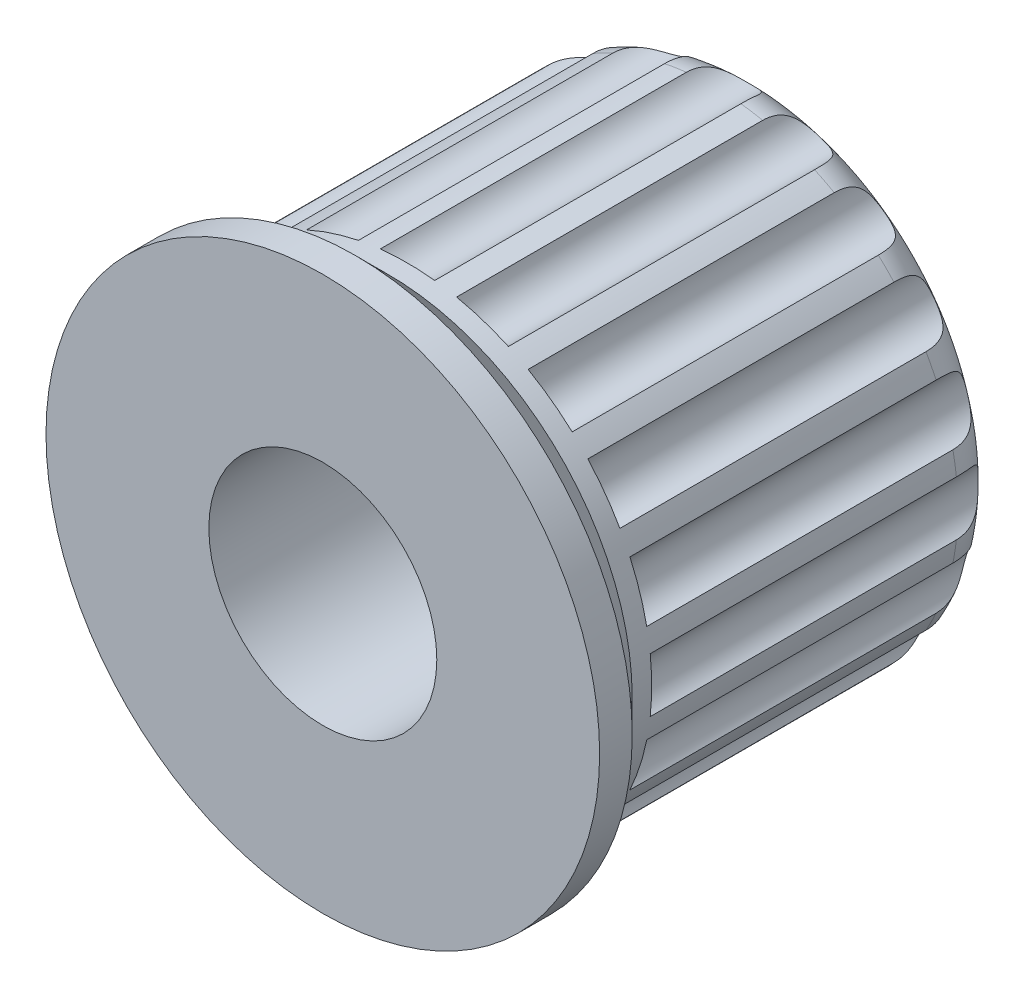
SolidWorks part; units mm, degrees
ref_plane "Front Plane" through (0, 0, 0) normal (0, 0, 1) x (1, 0, 0)
ref_plane "Top Plane" through (0, 0, 0) normal (0, 1, 0) x (1, 0, 0)
ref_plane "Right Plane" through (0, 0, 0) normal (1, 0, 0) x (0, 0, -1)
sketch "Sketch1" plane through (0, 0, 0) normal (0, 0, 1) x (1, 0, 0)
  circle A0 centre (0, 0) radius 2.975
  circle A1 centre (0, 0) radius 7.5
  dimension "D1" = 5.95
  dimension "D2" = 15
extrude "Boss-Extrude1" add sketch "Sketch1" along normal blind 2 contours A0 region at (0, 0, 0)
extrude "Boss-Extrude3" add sketch "Sketch1<3>" along normal offset from surface (13.5 mm away) 11.5 up to face at (2.975, 0, 2) offset beyond the face yes
sketch "Sketch1<3>" plane through (0, 0, 0) normal (0, 0, 1) x (1, 0, 0) same geometry as "Sketch1"
sketch "Sketch2" plane through (0, 0, 13.5) normal (0, 0, 1) x (1, 0, 0)
  circle A0 centre (0, 0) radius 3.5
  circle A1 centre (0, 0) radius 2.975 construction
  circle A2 centre (0, 0) radius 2.975
  dimension "D1" = 7
extrude "Cut-Extrude1" cut sketch "Sketch2" against normal offset from surface (5.5 mm away) 6 up to face at (2.975, 0, 2)
sketch "Sketch3" plane through (0, 0, 13.5) normal (0, 0, 1) x (1, 0, 0)
  circle A0 centre (0, 0) radius 7.5 construction
  circle A1 centre (0, 0) radius 7.5
  circle A2 centre (0, 0) radius 8.5
  dimension "D1" = 17
extrude "Boss-Extrude4" add sketch "Sketch3" against normal blind 2
fillet "Fillet2" radius 1.5 1 edges at (7.5, 0, 0)
sketch "Sketch5" plane through (0, 0, 0) normal (0, 0, -1) x (-1, 0, 0)
  circle A0 centre (0, 8) radius 1
  circle A2 centre (0, 0) radius 7.5 construction
  dimension "D2" = 2
  dimension "D1" = 0.5
extrude "Cut-Extrude2" cut sketch "Sketch5" against normal offset from surface (10.9 mm away) 0.6 up to face at (7.5, 0, 11.5)
pattern_circular "CirPattern1" count 20 over 360 about axis through (0, 0, 11.5) along (0, 0, 1) of "Cut-Extrude2"
chamfer "Chamfer1" distance 1 angle 45 1 edges at (8.5, 0, 11.5)
